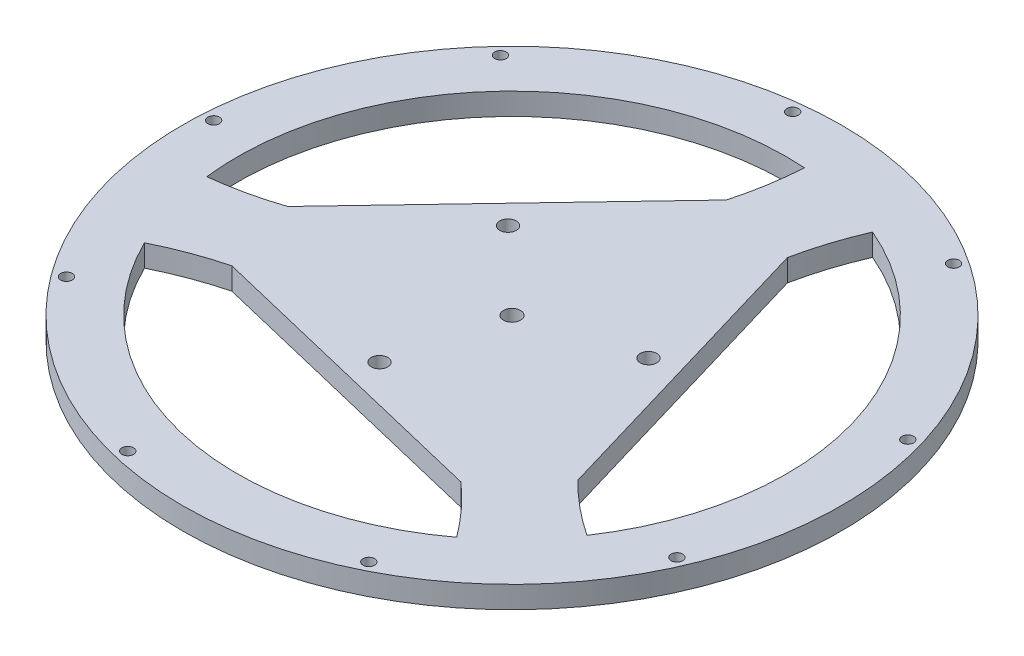
SolidWorks part; units mm, degrees
note: The reader was unsure of these and kept them because the rebuilt part matched: shared geometry of "草图3<17>", "草图3<22>", "草图3<23>".
ref_plane "前视基准面" through (0, 0, 0) normal (0, 0, 1) x (1, 0, 0)
ref_plane "上视基准面" through (0, 0, 0) normal (0, 1, 0) x (1, 0, 0)
ref_plane "右视基准面" through (0, 0, 0) normal (1, 0, 0) x (0, 0, -1)
other "Configuration Table"
sketch "草图3" plane through (0, 0, 0) normal (0, 1, 0) x (1, 0, 0)
  line L0 (0, 0) -> (-18.1254, 17.2183) construction
  line L1 (1.3258, 37.6943) -> (-37.5767, -3.2578)
  line L2 (-33.3071, -17.699) -> (21.6096, -30.9135)
  line L3 (31.9813, -19.9953) -> (15.967, 34.1712)
  line L4 (-18.1254, 17.2183) -> (-56.5061, 53.678) construction
  circle A2 centre (0, 0) radius 60
  arc A3 (3.374, 49.886) -> (-49.6473, -5.9287) centre (0, 0) ccw
  circle A4 centre (0, 0) radius 25 construction
  arc A6 (-49.6473, -5.9287) -> (-37.5767, -3.2578) centre (-56.5061, 53.678) ccw
  arc A7 (1.3258, 37.6943) -> (3.374, 49.886) centre (-56.5061, 53.678) ccw
  arc A8 (19.6892, 45.9601) -> (15.967, 34.1712) centre (74.7395, 22.0967) ccw
  arc A9 (31.9813, -19.9953) -> (41.5156, -27.865) centre (74.7395, 22.0967) ccw
  arc A10 (29.958, -40.0314) -> (21.6096, -30.9135) centre (-18.2335, -75.7747) ccw
  arc A11 (-33.3071, -17.699) -> (-44.8896, -22.021) centre (-18.2335, -75.7747) ccw
  arc A12 (41.5156, -27.865) -> (19.6892, 45.9601) centre (0, 0) ccw
  arc A13 (-44.8896, -22.021) -> (29.958, -40.0314) centre (0, 0) ccw
  circle A14 centre (-14.5003, 13.7746) radius 1.5
  circle A15 centre (19.1793, 5.6704) radius 1.5
  circle A16 centre (-4.679, -19.445) radius 1.5
  circle A17 centre (-42.051, 39.9464) radius 1.0529
  circle A26 centre (0, 0) radius 1.55
  circle A27 centre (-6.5359, 57.6306) radius 1.0529
  circle A28 centre (32.0374, 48.3488) radius 1.0529
  circle A29 centre (55.6201, 16.444) radius 1.0529
  circle A30 centre (53.1775, -23.155) radius 1.0529
  circle A31 centre (25.8526, -51.9196) radius 1.0529
  circle A32 centre (-13.5691, -56.3904) radius 1.0529
  circle A33 centre (-46.6416, -34.4755) radius 1.0529
  circle A34 centre (-57.89, 3.5708) radius 1.0529
  point P3 (-18.1254, 17.2183)
  point P6 (0, 0)
  point P11 (1.3258, 37.6943)
  point P12 (-37.5767, -3.2578)
  point P13 (-49.6473, -5.9287)
  point P14 (-59.6748, -6.2383)
  point P15 (3.1688, 59.9163)
  point P16 (3.374, 49.886)
  point P34 (0, 0)
  point P38 (0, 0)
  point P40 (0, 0)
  point P56 (0.9963, 4.1318)
  point P59 (0, 0)
  dimension "D1" = 120
  dimension "D2" = 100
  dimension "D5" = 60
  dimension "D6" = 56.9357
  dimension "D8" = 16.7809
  dimension "D10" = 3
  dimension "D15" = 2.1059
  dimension "D19" = 3.1
  dimension "D3" = 20
  dimension "D4" = 25
  dimension "D7" = 3
  dimension "D9" = 45.9601
  dimension "D12" = 19.445
  dimension "D13" = 19.1793
  dimension "D14" = 58
  dimension "D17" = 36.3755
  dimension "D18" = 12.5771
  dimension "D11" = 3
  dimension "D16" = 9
extrude "凸台-拉伸4" add sketch "草图3" along normal blind 4
extrude "切除-拉伸15" cut sketch "草图3<17>" along normal blind 4 contours L1 A7 A3 A6
sketch "草图3<17>" plane through (0, 0, 0) normal (0, 1, 0) x (1, 0, 0) same geometry as "草图3"
extrude "切除-拉伸23" cut sketch "草图3<22>" along normal blind 10 contours A26
sketch "草图3<22>" plane through (0, 0, 0) normal (0, 1, 0) x (1, 0, 0) same geometry as "草图3"
extrude "切除-拉伸24" cut sketch "草图3<23>" along normal blind 10 contours A34
sketch "草图3<23>" plane through (0, 0, 0) normal (0, 1, 0) x (1, 0, 0) same geometry as "草图3"
